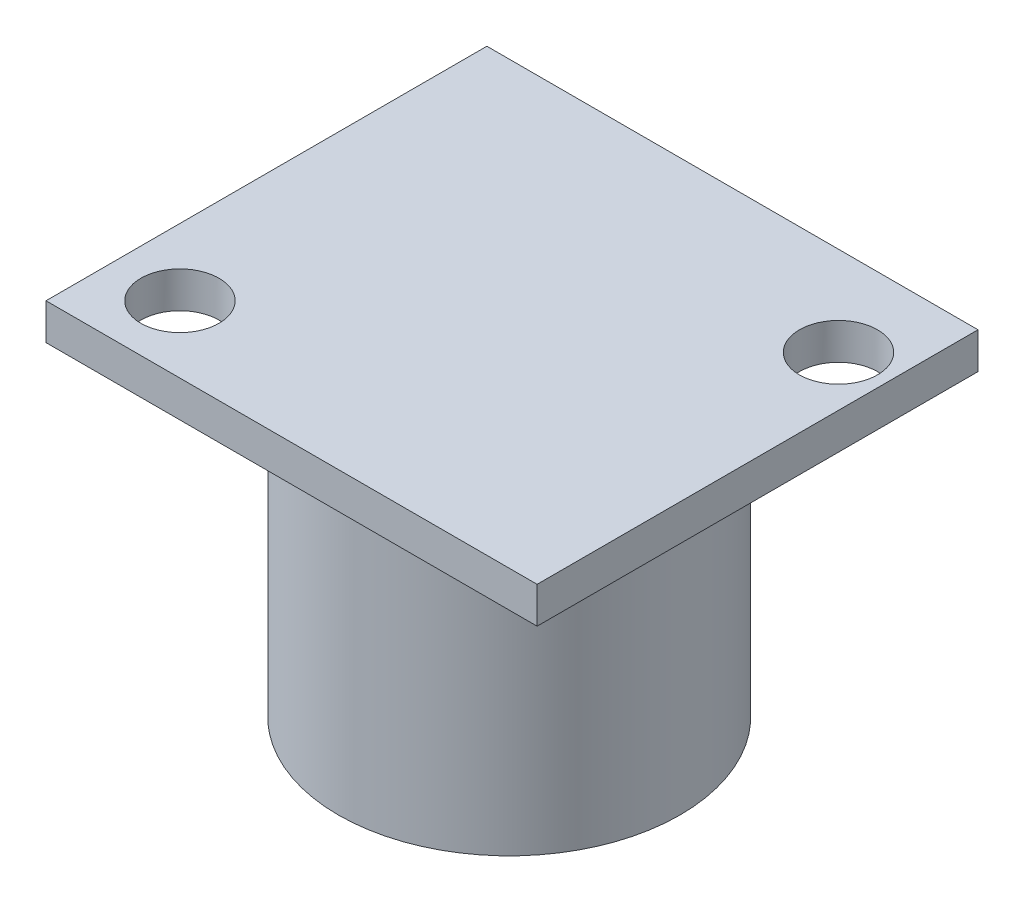
SolidWorks part; units mm, degrees
ref_plane "Front" through (0, 0, 0) normal (0, 0, 1) x (1, 0, 0)
ref_plane "Top" through (0, 0, 0) normal (0, 1, 0) x (1, 0, 0)
ref_plane "Right" through (0, 0, 0) normal (1, 0, 0) x (0, 0, -1)
sketch "Sketch1" plane through (0, 0, 0) normal (0, 1, 0) x (1, 0, 0)
  line L1 (0, 0) -> (22.352, 0)
  line L2 (0, 0) -> (0, 20.066)
  line L3 (0, 20.066) -> (22.352, 20.066)
  line L4 (22.352, 0) -> (22.352, 20.066)
  line L5 (0, 0) -> (22.352, 20.066) construction
  line L6 (0, 20.066) -> (22.352, 0) construction
  point P4 (11.176, 10.033)
  dimension "D1" = 20.066
  dimension "D2" = 22.352
extrude "Boss-Extrude1" add sketch "Sketch1" along normal blind 1.651
sketch "Sketch2" plane through (0, 1.651, 0) normal (0, 1, 0) x (1, 0, 0)
  line L0 (3.048, 1.27) -> (3.048, 0) construction
  line L2 (0, 0) -> (22.352, 0) construction
  line L4 (1.27, 3.048) -> (0, 3.048) construction
  line L5 (0, 20.066) -> (0, 0) construction
  circle A0 centre (3.048, 3.048) radius 1.778
  circle A1 centre (20.066, 16.002) radius 1.778
  point P12 (0, 0)
  dimension "D1" = 3.556
  dimension "D3" = 17.018
  dimension "D2" = 1.27
  dimension "D4" = 12.954
extrude "Cut-Extrude1" cut sketch "Sketch2" against normal up to next
sketch "Sketch3" plane through (0, 0, 0) normal (0, -1, 0) x (1, 0, 0)
  line L0 (3.048, -3.048) -> (20.066, -16.002) construction
  circle A0 centre (11.557, -9.525) radius 7.7756
  circle A1 centre (11.557, -9.525) radius 6.8622
extrude "Boss-Extrude2" add sketch "Sketch3" along normal blind 13.716
ref_axis "Axis1" through (11.557, -13.716, -9.525) along (0, 1, 0)
sketch "Sketch4" plane through (0, -13.716, 0) normal (0, -1, 0) x (1, 0, 0)
  circle A0 centre (11.557, -9.525) radius 6.8622 construction
  circle A1 centre (11.557, -9.525) radius 6.8622
  circle A2 centre (11.557, -9.525) radius 0.9847
  arc A3 (10.7379, -6.2356) -> (8.6653, -7.756) centre (11.557, -9.525) ccw construction
  arc A4 (10.6077, -5.713) -> (8.2059, -7.475) centre (11.557, -9.525) ccw
  arc A5 (10.868, -6.7582) -> (9.1247, -8.037) centre (11.557, -9.525) ccw
  arc A6 (10.868, -6.7582) -> (10.6077, -5.713) centre (10.7379, -6.2356) ccw
  arc A7 (8.2059, -7.475) -> (9.1247, -8.037) centre (8.6653, -7.756) ccw
  arc A8 (10.7379, -6.2356) -> (8.6653, -7.756) centre (11.557, -9.525) ccw construction
  arc A9 (10.6077, -5.713) -> (8.2059, -7.475) centre (11.557, -9.525) ccw
  arc A10 (10.868, -6.7582) -> (9.1247, -8.037) centre (11.557, -9.525) ccw
  arc A11 (10.868, -6.7582) -> (10.6077, -5.713) centre (10.7379, -6.2356) ccw
  arc A12 (8.2059, -7.475) -> (9.1247, -8.037) centre (8.6653, -7.756) ccw
  arc A13 (10.7379, -6.2356) -> (8.6653, -7.756) centre (11.557, -9.525) ccw construction
  arc A14 (10.6077, -5.713) -> (8.2059, -7.475) centre (11.557, -9.525) ccw
  arc A15 (10.868, -6.7582) -> (9.1247, -8.037) centre (11.557, -9.525) ccw
  arc A16 (10.868, -6.7582) -> (10.6077, -5.713) centre (10.7379, -6.2356) ccw
  arc A17 (8.2059, -7.475) -> (9.1247, -8.037) centre (8.6653, -7.756) ccw
  arc A18 (10.7379, -6.2356) -> (8.6653, -7.756) centre (11.557, -9.525) ccw construction
  arc A19 (10.6077, -5.713) -> (8.2059, -7.475) centre (11.557, -9.525) ccw
  arc A20 (10.868, -6.7582) -> (9.1247, -8.037) centre (11.557, -9.525) ccw
  arc A21 (10.868, -6.7582) -> (10.6077, -5.713) centre (10.7379, -6.2356) ccw
  arc A22 (8.2059, -7.475) -> (9.1247, -8.037) centre (8.6653, -7.756) ccw
  arc A23 (6.7175, -8.6267) -> (10.6587, -4.6855) centre (11.557, -9.525) cw construction
  arc A24 (10.5472, -4.085) -> (6.117, -8.5152) centre (11.557, -9.525) ccw
  arc A25 (10.7701, -5.2859) -> (7.3179, -8.7381) centre (11.557, -9.525) ccw
  arc A26 (10.7701, -5.2859) -> (10.5472, -4.085) centre (10.6587, -4.6855) ccw
  arc A27 (6.117, -8.5152) -> (7.3179, -8.7381) centre (6.7175, -8.6267) ccw
  arc A28 (12.4553, -4.6855) -> (16.3965, -8.6267) centre (11.557, -9.525) cw construction
  arc A29 (16.997, -8.5152) -> (12.5668, -4.085) centre (11.557, -9.525) ccw
  arc A30 (15.7961, -8.7381) -> (12.3439, -5.2859) centre (11.557, -9.525) ccw
  arc A31 (15.7961, -8.7381) -> (16.997, -8.5152) centre (16.3965, -8.6267) ccw
  arc A32 (12.5668, -4.085) -> (12.3439, -5.2859) centre (12.4553, -4.6855) ccw
  arc A33 (16.3965, -10.4233) -> (12.4553, -14.3645) centre (11.557, -9.525) cw construction
  arc A34 (12.5668, -14.965) -> (16.997, -10.5348) centre (11.557, -9.525) ccw
  arc A35 (12.3439, -13.7641) -> (15.7961, -10.3119) centre (11.557, -9.525) ccw
  arc A36 (12.3439, -13.7641) -> (12.5668, -14.965) centre (12.4553, -14.3645) ccw
  arc A37 (16.997, -10.5348) -> (15.7961, -10.3119) centre (16.3965, -10.4233) ccw
  arc A38 (10.6587, -14.3645) -> (6.7175, -10.4233) centre (11.557, -9.525) cw construction
  arc A39 (6.117, -10.5348) -> (10.5472, -14.965) centre (11.557, -9.525) ccw
  arc A40 (7.3179, -10.3119) -> (10.7701, -13.7641) centre (11.557, -9.525) ccw
  arc A41 (7.3179, -10.3119) -> (6.117, -10.5348) centre (6.7175, -10.4233) ccw
  arc A42 (10.5472, -14.965) -> (10.7701, -13.7641) centre (10.6587, -14.3645) ccw
  point P6 (9.5519, -6.7917)
  point P11 (11.557, -9.525)
  point P12 (8.0765, -6.0445)
  point P17 (9.5519, -6.7917)
  point P24 (9.5519, -6.7917)
  point P31 (9.5519, -6.7917)
  point P36 (11.176, -9.144)
  point P45 (15.0375, -6.0445)
  point P52 (15.0375, -13.0055)
  point P59 (8.0765, -13.0055)
  point P66 (11.557, -9.525)
  dimension "D1" = 4
  dimension "D2" = 4
extrude "Boss-Extrude3" add sketch "Sketch4" against normal blind 1.5875 rebuild error yes
